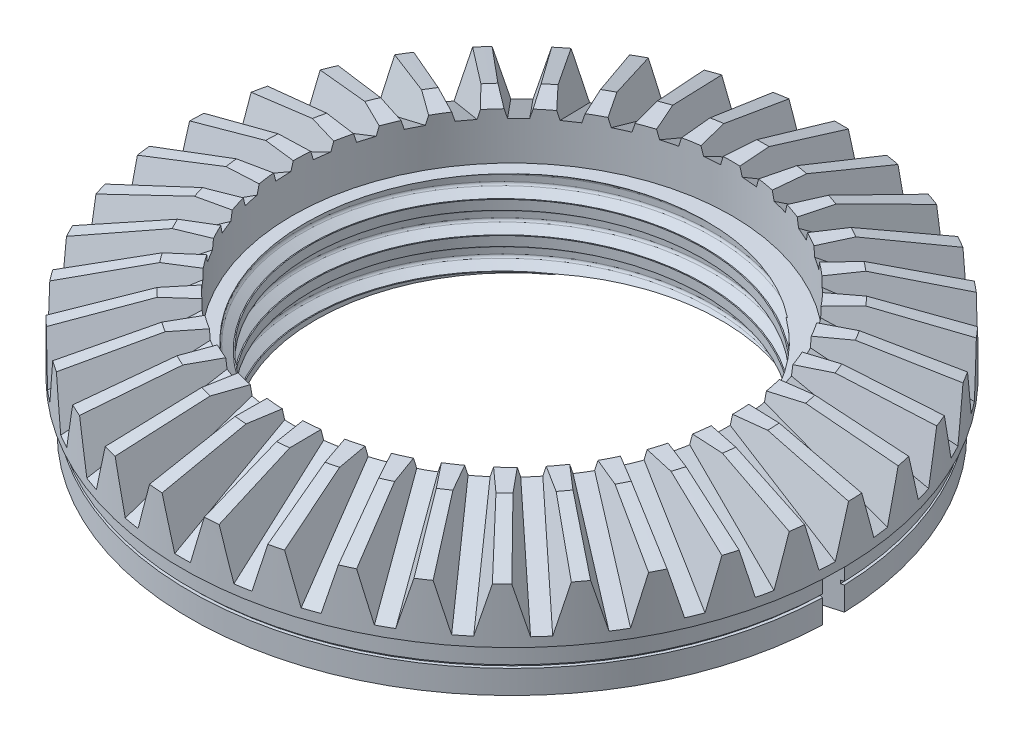
SolidWorks part; units mm, degrees
ref_plane "Front Plane" through (0, 0, 0) normal (0, 0, 1) x (1, 0, 0)
ref_plane "Top Plane" through (0, 0, 0) normal (0, 1, 0) x (1, 0, 0)
ref_plane "Right Plane" through (0, 0, 0) normal (1, 0, 0) x (0, 0, -1)
sketch "Sketch1" plane through (0, 0, 0) normal (0, 1, 0) x (1, 0, 0)
  circle A0 centre (0, 0) radius 21
  circle A1 centre (0, 0) radius 14
  dimension "D1" = 42
  dimension "D2" = 28
extrude "Boss-Extrude1" add sketch "Sketch1" along normal blind 8
sketch "Sketch2" plane through (0, 0, 0) normal (0, 0, 1) x (1, 0, 0)
  line L0 (16, 8) -> (21, 6.5)
  line L1 (21, 8) -> (-21, 8) construction
  line L2 (21, 0) -> (21, 8) construction
  line L3 (21, 6.5) -> (21, 8)
  line L4 (21, 8) -> (16, 8)
  line L5 (0, 0) -> (0, 8) construction
revolve "Cut-Revolve1" cut sketch "Sketch2" angle 360 about L5
sketch "Sketch3" plane through (0, 0, 0) normal (1, 0, 0) x (0, 0, -1)
  line L2 (0, 15.0777) -> (-25.8607, 0.7469) construction
ref_plane "Plane1" through (0, 0.7469, 25.8607) normal (0, -0.4847, 0.8747) x (1, 0, 0)
sketch "Sketch4" plane through (0, 0.7469, 25.8607) normal (0, -0.4847, 0.8747) x (1, 0, 0)
  line L0 (0, -13.1881) -> (0, 3.1271) construction
  line L1 (0, 3.1271) -> (-1.5, 3.1271)
  line L2 (-1.5, 3.1271) -> (-0.5, 0.1271)
  line L3 (-0.5, 0.1271) -> (0.5, 0.1271)
  line L4 (0.5, 0.1271) -> (1.5, 3.1271)
  line L5 (1.5, 3.1271) -> (0, 3.1271)
  dimension "D1" = 3
  dimension "D2" = 1.5
  dimension "D3" = 0.5
  dimension "D4" = 0.5
  dimension "D5" = 3
extrude "Cut-Extrude1" cut sketch "Sketch4" against normal blind 17 contours L5 L1 L2 L3 L4
pattern_circular "CirPattern1" count 37 over 360 about axis through (0, 6.5, 0) along (0, -1, 0) of "Cut-Extrude1"
sketch "Sketch5" plane through (0, 0, 0) normal (0, -1, 0) x (1, 0, 0)
  circle A0 centre (0, 0) radius 23.4023
  circle A1 centre (0, 0) radius 20.5
  dimension "D1" = 41
extrude "Cut-Extrude2" cut sketch "Sketch5" against normal blind 3
sketch "Sketch11" plane through (0, 0, 0) normal (0, -1, 0) x (1, 0, 0)
  line L0 (-20.488, 0.7) -> (-18, 0)
  line L1 (-18, 0) -> (-20.488, -0.7)
  line L2 (20.488, -0.7) -> (18, 0)
  line L3 (18, 0) -> (20.488, 0.7)
  circle A0 centre (0, 0) radius 20.5 construction
  circle A1 centre (0, 0) radius 20.5 construction
  arc A2 (-20.488, 0.7) -> (-20.488, -0.7) centre (0, 0) ccw
  arc A3 (20.488, -0.7) -> (20.488, 0.7) centre (0, 0) ccw
  point P14 (0, 0)
  dimension "D1" = 0.7
  dimension "D2" = 0
  dimension "D3" = 0.7
  dimension "D4" = 18
  dimension "D5" = 2
extrude "Cut-Extrude3" cut sketch "Sketch11" against normal blind 3
sketch "Sketch12" plane through (0, 0, 0) normal (0, -1, 0) x (1, 0, 0)
  circle A0 centre (0, 0) radius 20.5
  circle A1 centre (0, 0) radius 20.3
  dimension "D1" = 41
  dimension "D2" = 0.2
extrude "Cut-Extrude4" cut sketch "Sketch12" against normal blind 0.2 from offset 1.5 offset against normal yes
sketch "Sketch13" plane through (0, 0, 0) normal (0, -1, 0) x (1, 0, 0)
  circle A0 centre (0, 0) radius 12.5
  circle A1 centre (0, 0) radius 14
  dimension "D1" = 25
extrude "Boss-Extrude2" add sketch "Sketch13" against normal blind 5
sketch "Sketch14" plane through (0, 0, 0) normal (0, -1, 0) x (1, 0, 0)
  circle A0 centre (0, 0) radius 12.5 construction
  circle A1 centre (0, 0) radius 12.5
curve "Helix/Spiral1" pitch 2 height 5 radius 12.5 centre (0, 0, 0) axis (0, 1, 0) start towards (1, 0, 0)
ref_plane "Plane2" through (-12.5, 5, 0) normal (0, 0.0255, 0.9997) x (1, 0, 0)
sketch "Sketch15" plane through (-12.5, 5, 0) normal (0, 0.0255, 0.9997) x (1, 0, 0)
  line L0 (-0.0634, -0.7) -> (0.1568, -0.7)
  line L1 (-0.0634, 0.7) -> (-0.5851, 0.3592)
  line L2 (-0.6757, 0.1918) -> (-0.6757, -0.1918)
  line L3 (-0.5851, -0.3592) -> (-0.0634, -0.7)
  line L4 (0.1568, -0.7) -> (0.1568, 0.7)
  line L5 (0.1568, 0.7) -> (-0.0634, 0.7)
  arc A0 (-0.5851, 0.3592) -> (-0.6757, 0.1918) centre (-0.4757, 0.1918) ccw
  arc A1 (-0.6757, -0.1918) -> (-0.5851, -0.3592) centre (-0.4757, -0.1918) ccw
  point P14 (-0.6757, 0.3)
  point P17 (-0.6757, -0.3)
  dimension "D1" = 0.2
  dimension "D3" = 1.4
  dimension "D5" = 0.6
sweep "Cut-Sweep1" cut profiles "Sketch15" path "Helix/Spiral1" align with end faces yes
